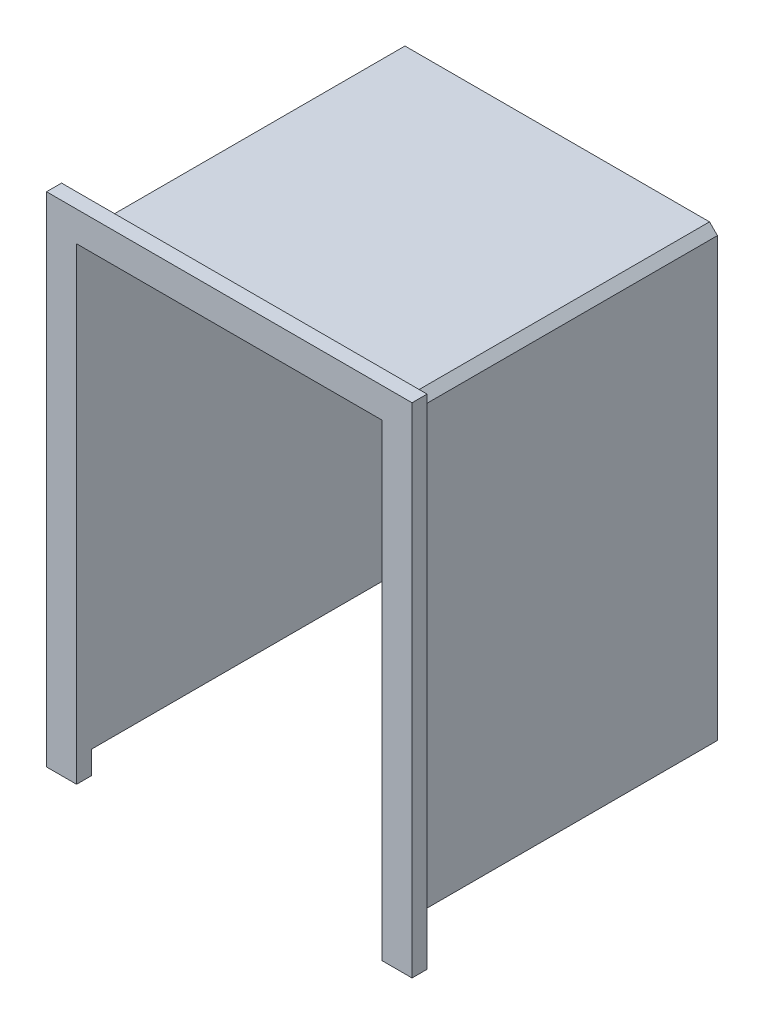
SolidWorks part; units mm, degrees
ref_plane "Plan de face" through (0, 0, 0) normal (0, 0, 1) x (1, 0, 0)
ref_plane "Plan de dessus" through (0, 0, 0) normal (0, 1, 0) x (1, 0, 0)
ref_plane "Plan de droite" through (0, 0, 0) normal (1, 0, 0) x (0, 0, -1)
sketch "Esquisse3" plane through (0, 0, 0) normal (0, 0, 1) x (1, 0, 0)
  line L5 (-64, 90.5) -> (64, 90.5)
  line L6 (-64, 90.5) -> (-64, -90.5)
  line L7 (-64, -90.5) -> (64, -90.5)
  line L8 (64, 90.5) -> (64, -90.5)
  point P4 (-64, 90.5)
  point P5 (64, -90.5)
  point P6 (-64, -90.5)
  point P7 (64, 90.5)
  dimension "D1" = 64
  dimension "D2" = 90.5
  dimension "D3" = 181
  dimension "D4" = 128
extrude "Boss.-Extru.4" add sketch "Esquisse3" against normal blind 131 contours L6 L7 L8 L5
shell "Coque2" thickness 3 removed face at (0, -90.5, -65.5) removed face at (0, 0, 0)
chamfer "Chanfrein1" distance 3.17 angle 45 4 edges at (64, -90.5, -65.5) (-64, -90.5, -65.5) (-64, 90.5, -65.5) (64, 90.5, -65.5)
sketch "Esquisse4" plane through (0, 0, 0) normal (0, 0, 1) x (1, 0, 0)
  line L0 (-60.83, 90.5) -> (60.83, 90.5) construction
  line L1 (-73, 99.5) -> (73, 99.5)
  line L2 (-73, 99.5) -> (-73, -99.5)
  line L3 (-73, -99.5) -> (73, -99.5)
  line L4 (73, 99.5) -> (73, -99.5)
  line L5 (-64, 87.33) -> (-64, -87.33) construction
  line L6 (64, 87.33) -> (64, -87.33) construction
  line L7 (-60.83, -90.5) -> (60.83, -90.5) construction
  line L8 (-64, 87.33) -> (-60.83, 90.5)
  line L9 (-60.83, 90.5) -> (60.83, 90.5)
  line L10 (60.83, 90.5) -> (64, 87.33)
  line L11 (64, 87.33) -> (64, -87.33)
  line L12 (64, -87.33) -> (61, -90.33)
  line L13 (61, -90.33) -> (-61, -90.33)
  line L14 (-61, -90.33) -> (-64, -87.33)
  line L15 (-64, 87.33) -> (-64, -87.33)
  dimension "D1" = 9
  dimension "D2" = 9
  dimension "D3" = 9
  dimension "D4" = 9
extrude "Boss.-Extru.5" add sketch "Esquisse4" against normal blind 6
sketch "Esquisse5" plane through (0, 0, 0) normal (0, 0, 1) x (1, 0, 0)
  line L0 (-61, -90.33) -> (-61, -99.5)
  line L1 (-73, -99.5) -> (73, -99.5) construction
  line L2 (61, -90.33) -> (61, -99.5)
  line L3 (-61, -90.33) -> (61, -90.33)
  line L4 (-61, -99.5) -> (61, -99.5)
extrude "Enlèv. mat.-Extru.1" cut sketch "Esquisse5" against normal blind 6 contours L3 L2 L4 L0
sketch "Esquisse6" plane through (0, 0, -128) normal (0, 0, 1) x (1, 0, 0)
  line L0 (-60.83, -90.5) -> (60.83, -90.5) construction
  line L1 (13, -90.5) -> (5, -90.5)
  line L2 (13, -90.5) -> (13, -50.5)
  line L3 (13, -50.5) -> (5, -50.5)
  line L4 (5, -90.5) -> (5, -50.5)
  line L5 (-61, 87.5) -> (-61, -99.5) construction
  line L6 (-5, -90.5) -> (-13, -90.5)
  line L7 (-5, -90.5) -> (-5, -50.5)
  line L8 (-5, -50.5) -> (-13, -50.5)
  line L9 (-13, -90.5) -> (-13, -50.5)
  line L10 (61, 87.5) -> (61, -99.5) construction
  dimension "D1" = 40
  dimension "D2" = 40
  dimension "D3" = 8
  dimension "D4" = 8
  dimension "D5" = 48
  dimension "D6" = 48
extrude "Boss.-Extru.6" add sketch "Esquisse6" along normal blind 40
sketch "Esquisse7" plane through (13, 0, 0) normal (1, 0, 0) x (0, 0, -1)
  line L0 (128, -50.5) -> (88, -65.5)
  line L1 (88, -90.5) -> (88, -50.5) construction
  line L2 (128, -90.5) -> (88, -75.5)
  line L3 (88, -65.5) -> (88, -50.5)
  line L4 (88, -50.5) -> (128, -50.5)
  line L5 (88, -75.5) -> (88, -90.5)
  line L6 (88, -90.5) -> (128, -90.5)
  point P8 (0, 0)
  dimension "D1" = 10
  dimension "D2" = 15
extrude "Enlèv. mat.-Extru.2" cut sketch "Esquisse7" against normal blind 26 contours L0 L3 L4 | L2 L5 L6
fillet "Congé2" radius 7.5 4 edges at (9, -75.5, -88) (-9, -75.5, -88) (-9, -65.5, -88) (9, -65.5, -88)
